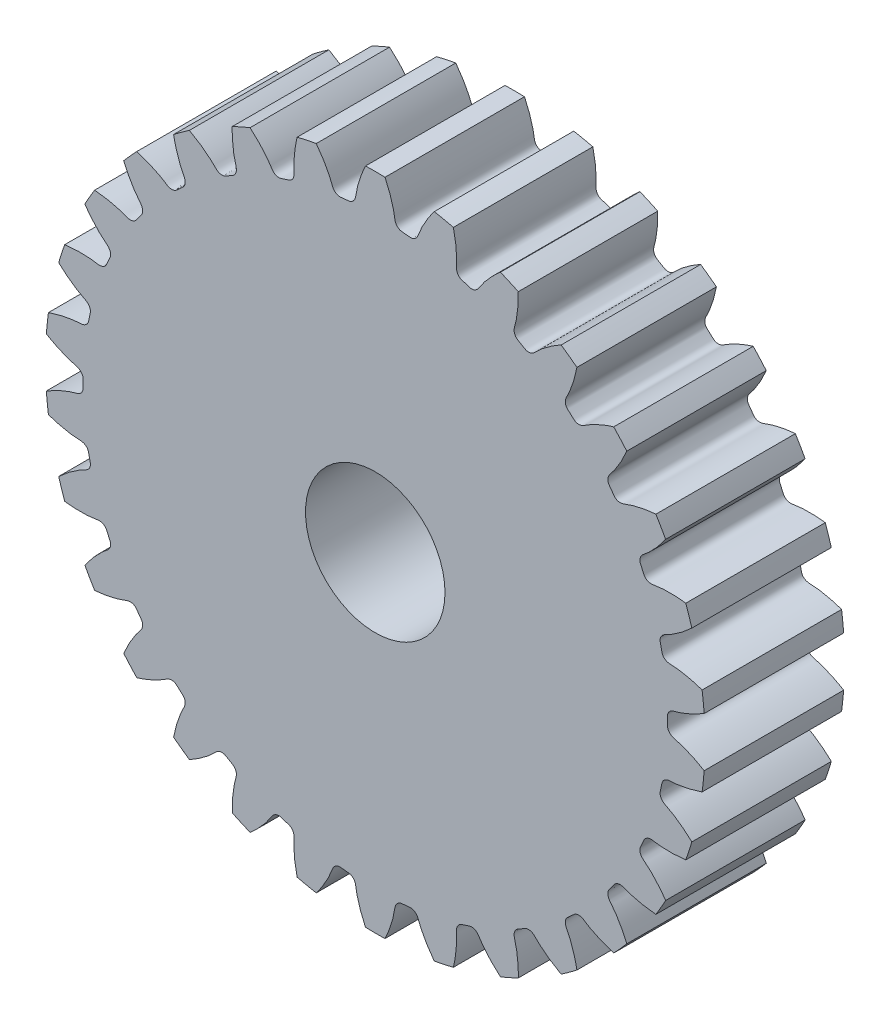
SolidWorks part; units mm, degrees
ref_plane "Front Plane" through (0, 0, 0) normal (0, 0, 1) x (1, 0, 0)
ref_plane "Top Plane" through (0, 0, 0) normal (0, 1, 0) x (1, 0, 0)
ref_plane "Right Plane" through (0, 0, 0) normal (1, 0, 0) x (0, 0, -1)
ref_axis "Axis1" through (0, 0, 55) along (0, 0, -1)
sketch "SketchRevolveGeartrax1Gear" plane through (0, 0, 0) normal (1, 0, 0) x (0, 0, -1)
  line L0 (0, 0) -> (1, 0) construction
  line L1 (-4, 0) -> (-4, 18.9152)
  line L2 (-4, 18.9152) -> (4, 18.9152)
  line L3 (4, 18.9152) -> (4, 0)
  line L4 (4, 0) -> (-4, 0)
  dimension "Side1" = 4
  dimension "OutsideRadius" = 18.9152
  dimension "Side2" = 4
revolve "Geartrax1Gear" add sketch "SketchRevolveGeartrax1Gear" angle 360 about L0
sketch "SketchToothGeartrax1Gear" plane through (0, 0, 0) normal (0, 0, 1) x (1, 0, 0)
  arc A0 (18.9078, 1.4474) -> (18.9078, -1.4474) centre (0, 0) cw
  spline S0 degree 3 poles (18.9078, -1.4474) (18.8217, -1.3946) (18.6936, -1.3191) (18.5234, -1.2249) (18.4018, -1.1606) (18.284, -1.101) (18.1702, -1.0459) (18.0604, -0.9952) (17.9548, -0.9488) (17.8535, -0.9065) (17.7567, -0.868) (17.6643, -0.8333) (17.5766, -0.8021) (17.4936, -0.7742) (17.4154, -0.7495) (17.3421, -0.728) (17.2431, -0.7002) (17.1573, -0.6817) (17.0869, -0.6575) (17.0577, -0.6461) (17.0283, -0.6331) (16.9986, -0.6181) (16.9682, -0.6004) (16.9369, -0.5793) (16.9045, -0.5537) (16.8713, -0.5219) (16.838, -0.4823) (16.8063, -0.4331) (16.7796, -0.3733) (16.7622, -0.3062) (16.7548, -0.1803) (16.7646, 0) (16.7548, 0.1803) (16.7622, 0.3062) (16.7796, 0.3733) (16.8063, 0.4331) (16.838, 0.4823) (16.8713, 0.5219) (16.9045, 0.5537) (16.9369, 0.5793) (16.9682, 0.6004) (16.9986, 0.6181) (17.0283, 0.6331) (17.0577, 0.6461) (17.0869, 0.6575) (17.1573, 0.6817) (17.2431, 0.7002) (17.3421, 0.728) (17.4154, 0.7495) (17.4936, 0.7742) (17.5766, 0.8021) (17.6643, 0.8333) (17.7567, 0.868) (17.8535, 0.9065) (17.9548, 0.9488) (18.0604, 0.9952) (18.1702, 1.0459) (18.284, 1.101) (18.4018, 1.1606) (18.5234, 1.2249) (18.6936, 1.3191) (18.8217, 1.3946) (18.9078, 1.4474) knots 0 0 0 0 0.054095 0.079654 0.10422 0.127794 0.150375 0.171963 0.192559 0.212162 0.230772 0.248391 0.265016 0.280649 0.295289 0.308937 0.321592 0.350363 0.355882 0.36146 0.367163 0.373075 0.379302 0.385981 0.393279 0.401399 0.410557 0.420948 0.432651 0.445522 0.457824 0.5 0.542176 0.554478 0.567349 0.579052 0.589443 0.598601 0.606721 0.614019 0.620698 0.626925 0.632837 0.63854 0.644118 0.649637 0.678408 0.691063 0.704711 0.719351 0.734984 0.751609 0.769228 0.787838 0.807441 0.828037 0.849625 0.872206 0.89578 0.920346 0.945905 1 1 1 1
extrude "ToothExtrudeCutGeartrax1Gear" cut sketch "SketchToothGeartrax1Gear" against normal blind 4 and the other way blind 4
pattern_circular "PatternGeartrax1Gear" count 30 every 12 about axis through (0, 0, 55) along (0, 0, -1) of "ToothExtrudeCutGeartrax1Gear"
sketch "BoreRevolveSketch" plane through (0, 0, 0) normal (1, 0, 0) x (0, 0, -1)
  line L0 (0, 0) -> (1, 0) construction
  line L1 (-4, 0) -> (4, 0)
  line L2 (4, 0) -> (4, 4)
  line L3 (4, 4) -> (-4, 4)
  line L4 (-4, 4) -> (-4, 0)
  dimension "BoreSide1" = 4
  dimension "TaperSide1" = 4
  dimension "BoreSide2" = 4
  dimension "TaperSide2" = 4
revolve "BoreRevolveCut" cut sketch "BoreRevolveSketch" angle 360 about L0
sketch "AuxiliarySketchGeartrax1Gear" plane through (0, 0, 0) normal (0, 0, 1) x (1, 0, 0)
  circle A0 centre (0, 0) radius 17.9575 construction
  circle A1 centre (0, 0) radius 16.8745 construction
  circle A2 centre (0, 0) radius 17.2004 construction
  circle A3 centre (0, 0) radius 18.9152 construction
  circle A4 centre (0, 0) radius 16.7603 construction
  dimension "PitchDiameter" = 35.915
  dimension "BaseDiameter" = 33.7491
  dimension "FormDiameter" = 34.4009
  dimension "MajorDiameter" = 37.8305
  dimension "MinorDiameter" = 33.5207
